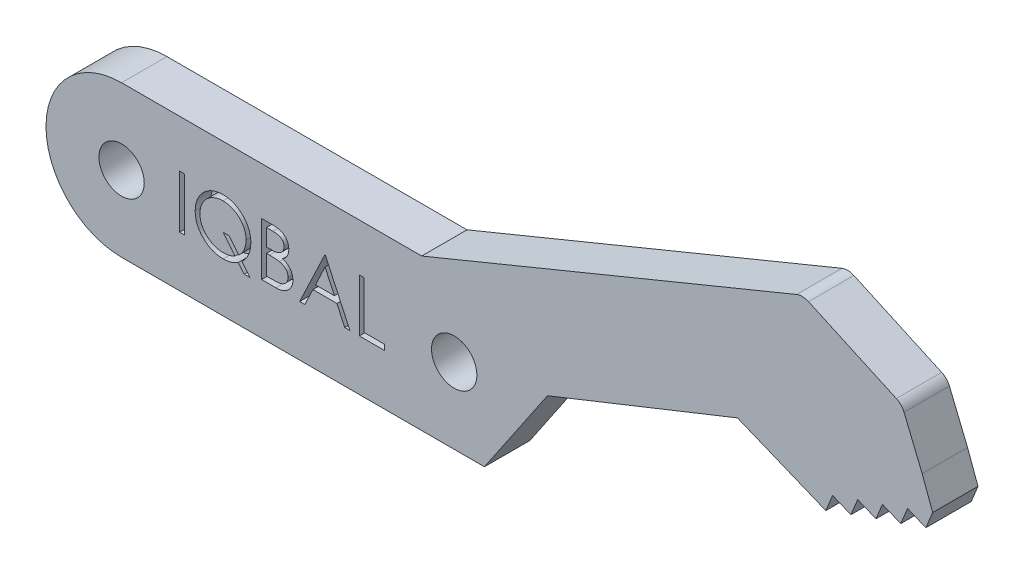
SolidWorks part; units mm, degrees
ref_plane "Front Plane" through (0, 0, 0) normal (0, 0, 1) x (1, 0, 0)
ref_plane "Top Plane" through (0, 0, 0) normal (0, 1, 0) x (1, 0, 0)
ref_plane "Right Plane" through (0, 0, 0) normal (1, 0, 0) x (0, 0, -1)
sketch "Sketch1" plane through (0, 0, 0) normal (0, 0, 1) x (1, 0, 0)
  line L0 (0, 0) -> (22, 0) construction
  line L1 (0, 5) -> (19.85, 5)
  line L2 (0, -5) -> (22, -5)
  line L3 (19.85, 5) -> (44.6431, 15.1937)
  line L4 (45.4379, 15.1788) -> (51.2451, 12.5335)
  line L5 (51.7554, 12.0038) -> (52.955, 9.0863)
  line L6 (24, -5) -> (22, -5)
  line L7 (24, -5) -> (28.1744, 1.1586)
  line L8 (28.1744, 1.1586) -> (40.742, 6.17)
  line L9 (40.742, 6.17) -> (46.5818, 3.7797)
  line L10 (46.5818, 3.7797) -> (47.0288, 4.8718)
  line L11 (47.0288, 4.8718) -> (48.2418, 4.3753)
  line L12 (48.2418, 4.3753) -> (48.6888, 5.4674)
  line L13 (48.6888, 5.4674) -> (49.9018, 4.9709)
  line L14 (49.9018, 4.9709) -> (50.3274, 6.0107)
  line L15 (50.3274, 6.0107) -> (51.5404, 5.5142)
  line L16 (51.5404, 5.5142) -> (51.9874, 6.6063)
  line L17 (51.9874, 6.6063) -> (53.2004, 6.1098)
  line L18 (53.2004, 6.1098) -> (53.6474, 7.2018)
  line L19 (53.6474, 7.2018) -> (52.955, 9.0863)
  arc A0 (0, 5) -> (0, -5) centre (0, 0) ccw
  circle A2 centre (0, 0) radius 1.5
  circle A3 centre (22, 0) radius 1.5
  arc A4 (51.2451, 12.5335) -> (51.7554, 12.0038) centre (50.8306, 11.6235) cw
  arc A5 (44.6431, 15.1937) -> (45.4379, 15.1788) centre (45.0233, 14.2688) cw
  point P3 (11, 0)
  point P18 (51.605, 12.3696)
  point P21 (45.0437, 15.3584)
  point P22 (24, -5)
  dimension "D3" = 3
  dimension "D4" = 3
  dimension "D12" = 1
  dimension "D2" = 5
  dimension "D5" = 19.85
  dimension "D6" = 157.65
  dimension "D7" = 27.24
  dimension "D8" = 133.16
  dimension "D9" = 7.21
  dimension "D10" = 136.84
  dimension "D11" = 3.55
  dimension "D13" = 24
  dimension "D14" = 55.87
  dimension "D15" = 7.44
  dimension "D16" = 214.13
  dimension "D17" = 13.53
  dimension "D18" = 224
  dimension "D19" = 6.31
  dimension "D20" = 1.18
  dimension "D21" = 1.66
  dimension "D22" = 2.0076
  dimension "D23" = 10
  dimension "D24" = 22
extrude "Boss-Extrude1" add sketch "Sketch1" along normal blind 3
sketch "Sketch2" plane through (0, 0, 3) normal (0, 0, 1) x (1, 0, 0)
  text T0 "IQBAL"
extrude "Cut-Extrude1" cut sketch "Sketch2" against normal blind 1
